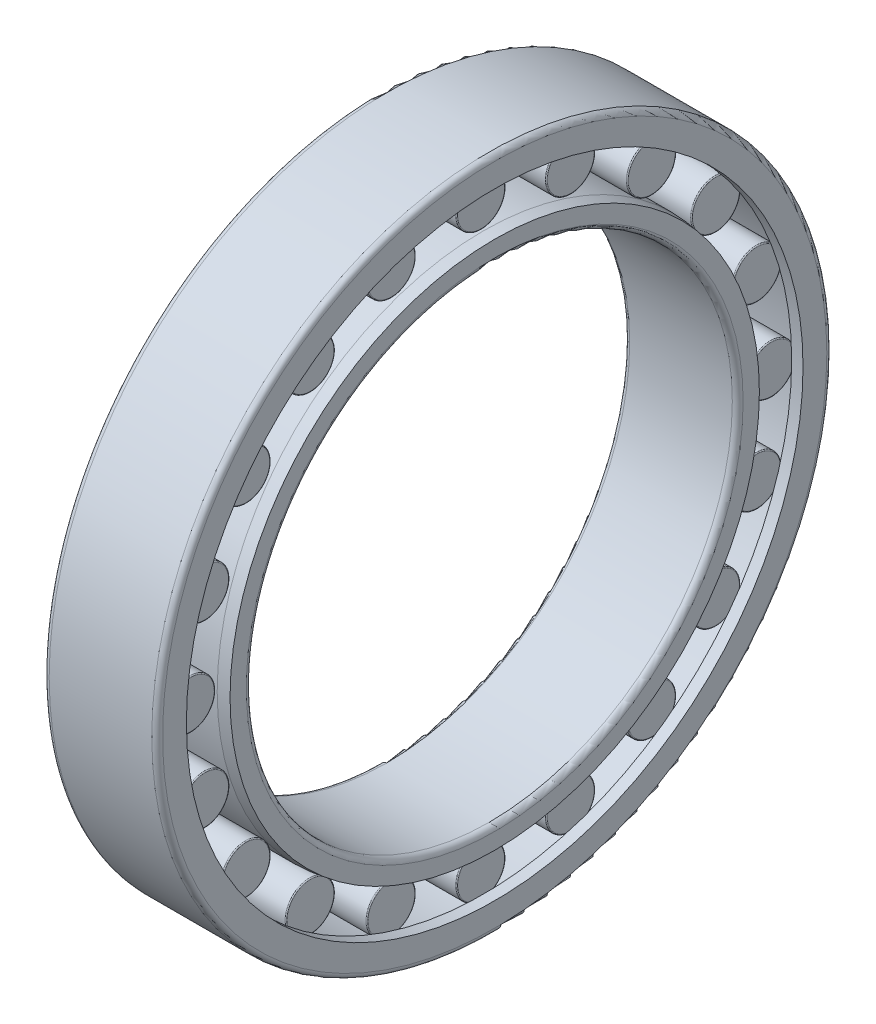
SolidWorks part; units mm, degrees
ref_plane "Plane1" through (0, 0, 0) normal (0, 0, 1) x (1, 0, 0)
ref_plane "Plane2" through (0, 0, 0) normal (0, 1, 0) x (1, 0, 0)
ref_plane "Plane3" through (0, 0, 0) normal (1, 0, 0) x (0, 0, -1)
sketch "Clipboard" plane through (0, 0, 0) normal (0, 0, 1) x (1, 0, 0)
  line L0 (-10, 0) -> (10, 0) construction
  line L1 (0, 0) -> (185.2698, -67.4327)
  line L2 (0, 0) -> (101.017, 36.7672)
  line L3 (0, 0) -> (218.798, -79.636)
  line L4 (0, 0) -> (-22.3471, -0.7804)
  dimension "Race_OD" = 232.84
  dimension "Race_ID" = 197.16
sketch "OutRacSke" plane through (0, 0, 0) normal (0, 0, 1) x (1, 0, 0)
  line L0 (-16.8, 114.1887) -> (-21, 114.1887)
  line L1 (-21, 114.1887) -> (-21, 123)
  line L2 (-19, 125) -> (19, 125)
  line L3 (21, 123) -> (21, 114.1888)
  line L4 (21, 114.1888) -> (16.8, 114.1888)
  line L5 (16.8, 114.1888) -> (16.8, 116.42)
  line L6 (16.8, 116.42) -> (-16.8, 116.42)
  line L7 (-16.8, 116.42) -> (-16.8, 114.1887)
  line L8 (-90, 0) -> (90, 0) construction
  arc A0 (-21, 123) -> (-19, 125) centre (-19, 123) cw
  arc A1 (19, 125) -> (21, 123) centre (19, 123) cw
  dimension "Race_OD" = 232.84
  dimension "radius" = 2
  dimension "halfWidth" = 21
  dimension "Cyl_Len" = 33.6
revolve "OuterRace" add sketch "OutRacSke" angle 360 about L8 reverse direction yes
sketch "RolDetSke" plane through (0, 0, 0) normal (0, 0, 1) x (1, 0, 0)
  line L0 (-15.96, 116.1851) -> (-15.96, 107.5)
  line L1 (-15.96, 107.5) -> (15.96, 107.5)
  line L2 (15.96, 107.5) -> (15.96, 116.1851)
  line L3 (15.5981, 116.547) -> (-15.5981, 116.547)
  line L4 (-33.6, 107.5) -> (33.6, 107.5) construction
  arc A0 (15.96, 116.1851) -> (15.5981, 116.547) centre (15.5981, 116.1851) ccw
  arc A1 (-15.5981, 116.547) -> (-15.96, 116.1851) centre (-15.5981, 116.1851) ccw
  dimension "radius" = 0.3619
  dimension "Roller_diameter" = 18.094
  dimension "halfLength" = 15.96
revolve "RollerDetailed" add sketch "RolDetSke" angle 360 about L4 reverse direction yes
ref_axis "Axis1" through (-50, 0, 0) along (1, 0, 0)
sketch "RolSimSke" plane through (0, 101.6, 0) normal (0, 0, 1) x (1, 0, 0)
  line L0 (-15.96, 14.5851) -> (-15.96, -2.7851)
  line L1 (25.4, -101.6) -> (-25.4, -101.6) construction
  line L2 (15.96, -2.7851) -> (15.96, 14.5851)
  line L3 (15.5981, 14.947) -> (-15.5981, 14.947)
  line L5 (15.5981, -3.147) -> (-15.5981, -3.147)
  arc A0 (15.96, 14.5851) -> (15.5981, 14.947) centre (15.5981, 14.5851) ccw
  arc A1 (-15.5981, 14.947) -> (-15.96, 14.5851) centre (-15.5981, 14.5851) ccw
  arc A2 (15.96, -2.7851) -> (15.5981, -3.147) centre (15.5981, -2.7851) cw
  arc A3 (-15.5981, -3.147) -> (-15.96, -2.7851) centre (-15.5981, -2.7851) cw
  dimension "radius" = 0.3619
  dimension "D1" = 98.453
  dimension "Roller_diameter" = 18.094
  dimension "halfLength" = 15.96
revolve "RollersSimplified" [suppressed] add sketch "RolSimSke" angle 360 about L1
sketch "InsRacSke" plane through (0, 0, 0) normal (0, 0, 1) x (1, 0, 0)
  line L0 (-16.8, 98.58) -> (-21, 98.0222)
  line L1 (-21, 98.0222) -> (-21, 92)
  line L2 (-19, 90) -> (19, 90)
  line L3 (21, 92) -> (21, 98.0222)
  line L4 (21, 98.0222) -> (16.8, 98.58)
  line L5 (16.8, 98.58) -> (-16.8, 98.58)
  line L6 (-90, 0) -> (90, 0) construction
  arc A0 (-21, 92) -> (-19, 90) centre (-19, 92) ccw
  arc A1 (19, 90) -> (21, 92) centre (19, 92) ccw
  dimension "radius" = 2
  dimension "Race_ID" = 197.16
  dimension "Width" = 42
  dimension "halfWidth" = 21
  dimension "groove_dp" = 0.5578
  dimension "Cyl_Len" = 33.6
revolve "InnerRace" add sketch "InsRacSke" angle 360 about L6 reverse direction yes
pattern_circular "RollersDetailed" count 20 every 18 about axis through (-50, 0, 0) along (1, 0, 0) of "RollerDetailed"
sketch "CagSpiSke" plane through (0, 0, 0) normal (0, 0, 1) x (1, 0, 0)
  line L0 (18.9, 105.2383) -> (18.9, 109.7618)
  line L1 (18.9, 109.7618) -> (-18.9, 109.7618)
  line L2 (-18.9, 109.7618) -> (-18.9, 105.2383)
  line L3 (-18.9, 105.2383) -> (18.9, 105.2383)
  line L4 (-90, 0) -> (90, 0) construction
revolve "CageSpine" [suppressed] add sketch "CagSpiSke" angle 360 about L4
equation "\"CLdia@Clipboard\" =  ( \"Race_OD@Clipboard\" + \"Race_ID@Clipboard\" )  / 4"
equation "\"Race_OD@OutRacSke\" = \"Race_OD@Clipboard\""
equation "\"halfCylLen@OutRacSke\" = \"Cyl_Len@OutRacSke\" / 2"
equation "\"RolCLRad@RolDetSke\" = \"CLdia@Clipboard\""
equation "\"Roller_diameter@RolDetSke\" =  ( \"Race_OD@Clipboard\" - \"Race_ID@Clipboard\" )  / 2 + .01"
equation "\"Roller_diameter@RolSimSke\" =  ( \"Race_OD@Clipboard\" - \"Race_ID@Clipboard\" )  / 2 + .01"
equation "\"radius@RolDetSke\" = \"Roller_diameter@RolDetSke\" / 50"
equation "\"Length@RolDetSke\" = \"Cyl_Len@OutRacSke\" * .95"
equation "\"halfLength@RolDetSke\" = \"Length@RolDetSke\" / 2"
equation "\"thickness@CagSpiSke\"  = \"Roller_diameter@RolDetSke\" * .25"
equation "\"Cag_IR@CagSpiSke\" =  \"RolCLRad@RolDetSke\" * 2 - \"thickness@CagSpiSke\""
equation "\"Rol_Length@RolSimSke\" = \"Cyl_Len@InsRacSke\" * .95"
equation "\"halfLength@RolSimSke\" = \"Rol_Length@RolSimSke\" / 2"
equation "\"radius@RolSimSke\" = \"radius@RolDetSke\""
equation "\"D1@RolSimSke\" = \"CLdia@Clipboard\" -  ( \"Roller_diameter@RolSimSke\" / 2 ) "
equation "\"Max_count@Clipboard\" = int( 3.14159265 / atn(( \"Roller_diameter@RolDetSke\" / 2) / sqr( \"RolCLRad@RolDetSke\"  *  \"RolCLRad@RolDetSke\" - ( \"Roller_diameter@RolDetSke\" / 2) *  ( \"Roller_diameter@RolDetSke\" / 2))))"
equation "\"Max_count@Clipboard\" = ((sgn( \"Max_count@Clipboard\" - \"Count@Clipboard\" )-1)*( \"Max_count@Clipboard\" - \"Count@Clipboard\" ))/-2+ \"Count@Clipboard\""
equation "\"Count@RollersDetailed\" = int( \"Show_count@Clipboard\" ) "
equation "\"Count@RollersDetailed\" = ((sgn( \"Count@RollersDetailed\" - \"Max_count@Clipboard\" )-1)*( \"Count@RollersDetailed\" - \"Max_count@Clipboard\" ))/-2+ \"Max_count@Clipboard\""
equation "\"Count@RollersDetailed\" = ((sgn( \"Count@RollersDetailed\" - \"Min_count@Clipboard\" )+1)*( \"Count@RollersDetailed\" - \"Min_count@Clipboard\"))/2 +\"Min_count@Clipboard\""
equation "\"Angle@RollersDetailed\" = 360.0 / \"Max_count@Clipboard\""
equation "\"radius@InsRacSke\" = \"radius@OutRacSke\""
equation "\"groove_dp@InsRacSke\" = \"groove_dp@OutRacSke\" / 4"
equation "\"Width@InsRacSke\" = \"Width@OutRacSke\""
equation "\"halfWidth@OutRacSke\" = \"Width@OutRacSke\" / 2"
equation "\"halfWidth@InsRacSke\" = \"Width@InsRacSke\" / 2"
equation "\"Race_ID@InsRacSke\" = \"Race_ID@Clipboard\""
equation "\"Cyl_Len@InsRacSke\" = \"Cyl_Len@OutRacSke\""
equation "\"Angle@CageSpine\" =  \"Angle@RollersDetailed\" * ( \"Count@RollersDetailed\" -1 + int( \"Count@RollersDetailed\" / \"Max_count@Clipboard\" ) )  + 0.001 -  int( \"Count@RollersDetailed\" / \"Max_count@Clipboard\" ) * 0.001"
equation "\"Angle@CageSpine\" =  \"Angle@CageSpine\" * int( \"Min_count@Clipboard\" / 2) + int(1 / \"Min_count@Clipboard\")  * 0.001"
equation "\"width@CagSpiSke\" =   ( \"Width@InsRacSke\" + \"Cyl_Len@InsRacSke\" )  / 2"
equation "\"halfwidth@CagSpiSke\" = \"width@CagSpiSke\" / 2"
